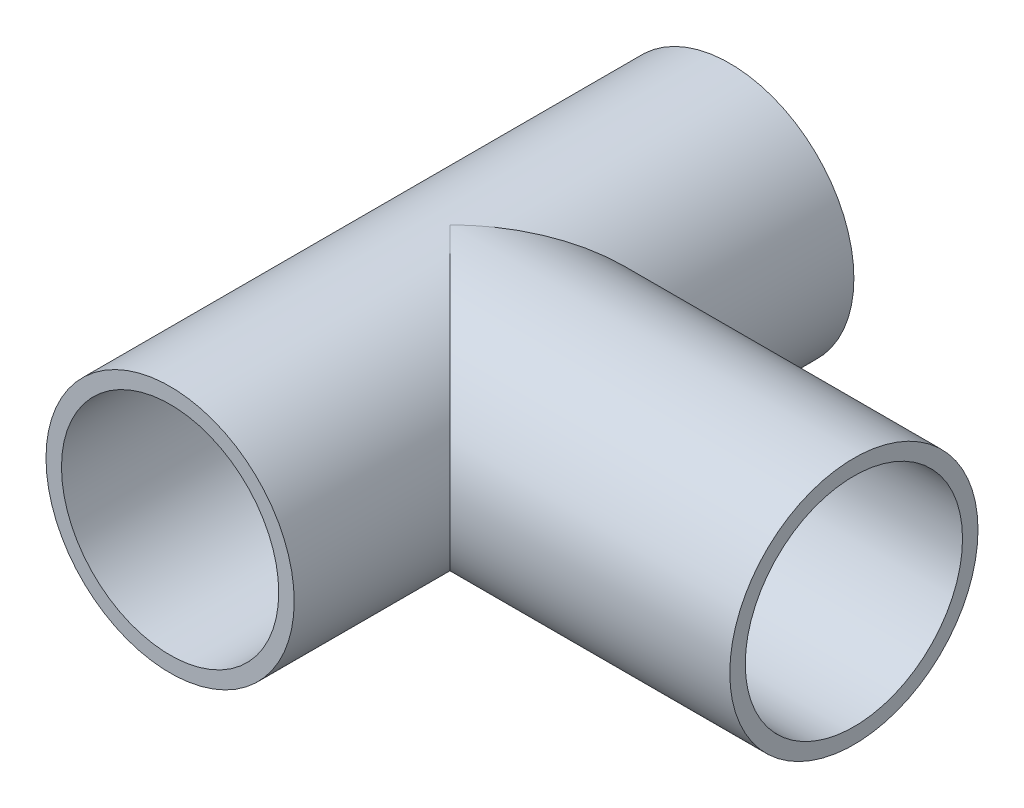
SolidWorks part; units mm, degrees
material "PE High Density"
ref_plane "Front Plane" through (0, 0, 0) normal (0, 0, 1) x (1, 0, 0)
ref_plane "Top Plane" through (0, 0, 0) normal (0, 1, 0) x (1, 0, 0)
ref_plane "Right Plane" through (0, 0, 0) normal (1, 0, 0) x (0, 0, -1)
other "Center of Mass"
sketch "Through Section" plane through (0, 0, 0) normal (0, 0, 1) x (1, 0, 0)
  circle A0 centre (0, 0) radius 161.925
  circle A1 centre (0, 0) radius 141.732
  dimension "D1" = 283.464
  dimension "D2" = 323.85
extrude "Through Section Extrude" add sketch "Through Section" along normal mid plane 730.25
ref_plane "E Plane" through (527.05, 0, 0) normal (1, 0, 0) x (0, 0, -1)
sketch "Orthogonal Section OD" plane through (527.05, 0, 0) normal (1, 0, 0) x (0, 0, -1)
  circle A0 centre (0, 0) radius 161.925
  dimension "D3" = 323.85
extrude "Orthogonal Section OD Extrude" add sketch "Orthogonal Section OD" against normal up to surface (365.125 mm away) up to face at (161.925, 0, 365.125)
sketch "Orthogonal Section ID" plane through (527.05, 0, 0) normal (1, 0, 0) x (0, 0, -1)
  circle A0 centre (0, 0) radius 141.732
  circle A1 centre (0, 0) radius 161.925 construction
  dimension "D1" = 283.464
extrude "Orthogonal Section ID Cut" cut sketch "Orthogonal Section ID" against normal up to surface (527.05 mm away) up to plane "Right Plane"
other "Center of Mass Reference Point1"
ref_plane "Plane1" [suppressed] through (0, 0, -365.125) normal (0, 0, -1) x (-1, 0, 0)
ref_plane "Plane2" [suppressed] through (0, 0, 365.125) normal (0, 0, 1) x (1, 0, 0)
ref_plane "Plane3" [suppressed] through (527.05, 0, 0) normal (1, 0, 0) x (0, 0, -1)
other "Intersect1" [suppressed]
equation "\"ID\"= 11.160in'EPG"
equation "\"OD\"= 12.75in'EPG"
equation "\"A\"= 8in'EPG"
equation "\"C\"= 28.75in'EPG"
equation "\"E\"= 8in'EPG"
equation "\"D1@Through Section\" = \"ID\""
equation "\"D2@Through Section\" = \"OD\""
equation "\"D1@Through Section Extrude\" = \"C\""
equation "\"D3@Orthogonal Section OD\" = \"OD\""
equation "\"D1@Orthogonal Section ID\" = \"ID\""
